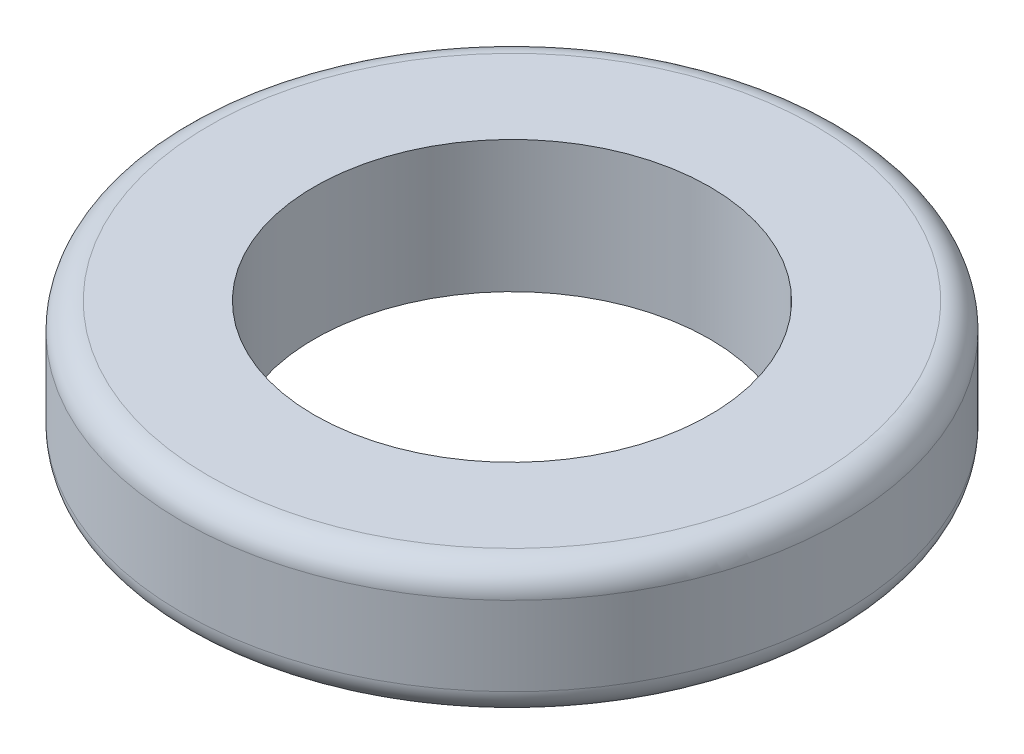
SolidWorks part; units mm, degrees
ref_plane "Front Plane" through (0, 0, 0) normal (0, 0, 1) x (1, 0, 0)
ref_plane "Top Plane" through (0, 0, 0) normal (0, 1, 0) x (1, 0, 0)
ref_plane "Right Plane" through (0, 0, 0) normal (1, 0, 0) x (0, 0, -1)
ref_axis "X-Axis" through (88.99, 0, 0) along (-1, 0, 0)
ref_axis "Y-Axis" through (0, 0, -88.99) along (0, 0, 1)
ref_axis "Z-Axis" through (0, -55, 0) along (0, 1, 0)
sketch "Sketch1" plane through (0, 0, 0) normal (0, 1, 0) x (1, 0, 0)
  circle A0 centre (0, 0) radius 7.5
  circle A1 centre (0, 0) radius 12.5
  dimension "D1" = 15
  dimension "D2" = 25
extrude "Boss-Extrude1" add sketch "Sketch1" along normal blind 5
fillet "Fillet1" radius 1 2 edges at (0, 0, 12.5) (0, 5, 12.5)
